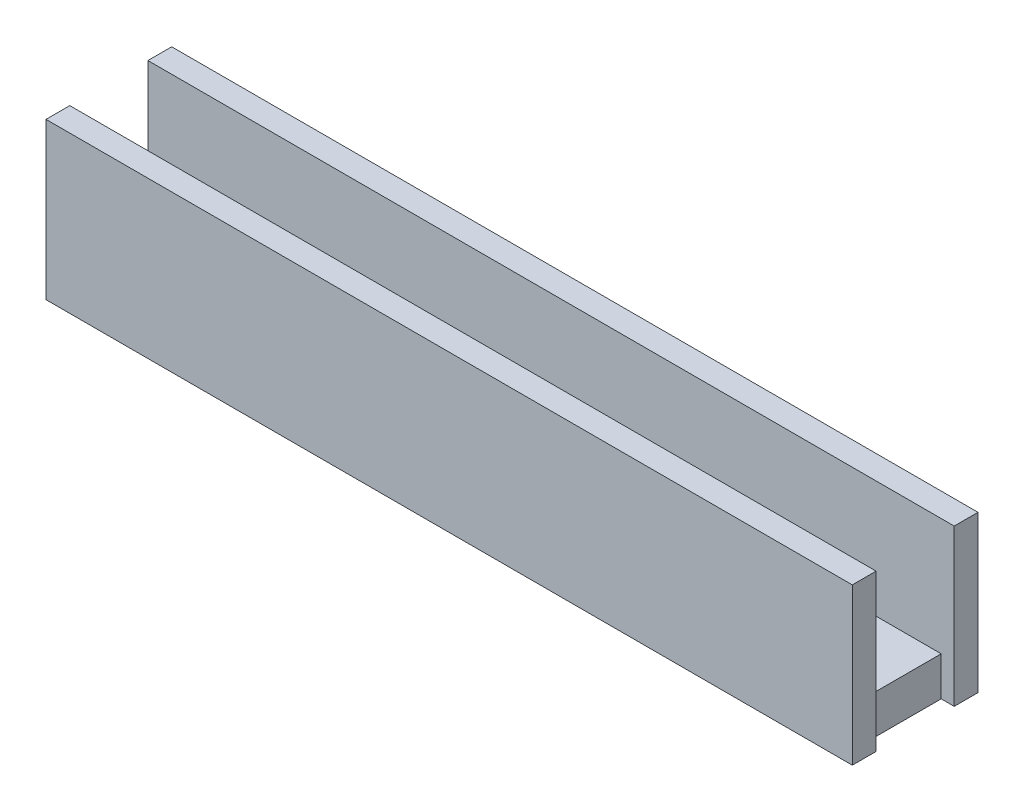
SolidWorks part; units mm, degrees
ref_plane "Front Plane" through (0, 0, 0) normal (0, 0, 1) x (1, 0, 0)
ref_plane "Top Plane" through (0, 0, 0) normal (0, 1, 0) x (1, 0, 0)
ref_plane "Right Plane" through (0, 0, 0) normal (1, 0, 0) x (0, 0, -1)
sketch "Sketch1" plane through (0, 0, 0) normal (0, 1, 0) x (1, 0, 0)
  line L0 (-0.7927, -5) -> (50.8328, -5)
  line L1 (0, 0) -> (50, 0)
  line L2 (0, 0) -> (0, -5)
  line L3 (0, -5) -> (50, -5)
  line L4 (50, 0) -> (50, -5)
  line L5 (-0.7927, 1.524) -> (50.8328, 1.524)
  line L6 (-0.7927, 1.524) -> (-0.7927, 0)
  line L7 (-0.7927, 0) -> (50.8328, 0)
  line L8 (50.8328, 1.524) -> (50.8328, 0)
  line L9 (50.8328, -5) -> (50.8328, -6.524)
  line L10 (50.8328, -6.524) -> (-0.7927, -6.524)
  line L11 (-0.7927, -6.524) -> (-0.7927, -5)
  dimension "D1" = 50
  dimension "D2" = 5
  dimension "D3" = 1.524
  dimension "D4" = 1.524
  dimension "D5" = 51.6255
extrude "Boss-Extrude1" add sketch "Sketch1" along normal blind 2.5 contours L4 L1 L2 L3 region at (25, 0, 2.5)
extrude "Boss-Extrude2" add sketch "Sketch1<3>" along normal blind 10 separate body contours L8 L5 L6 L7 L1 | L10 L11 L0 L9 region at (25.0201, 0, -0.762)
sketch "Sketch1<3>" plane through (0, 0, 0) normal (0, 1, 0) x (1, 0, 0) same geometry as "Sketch1"
